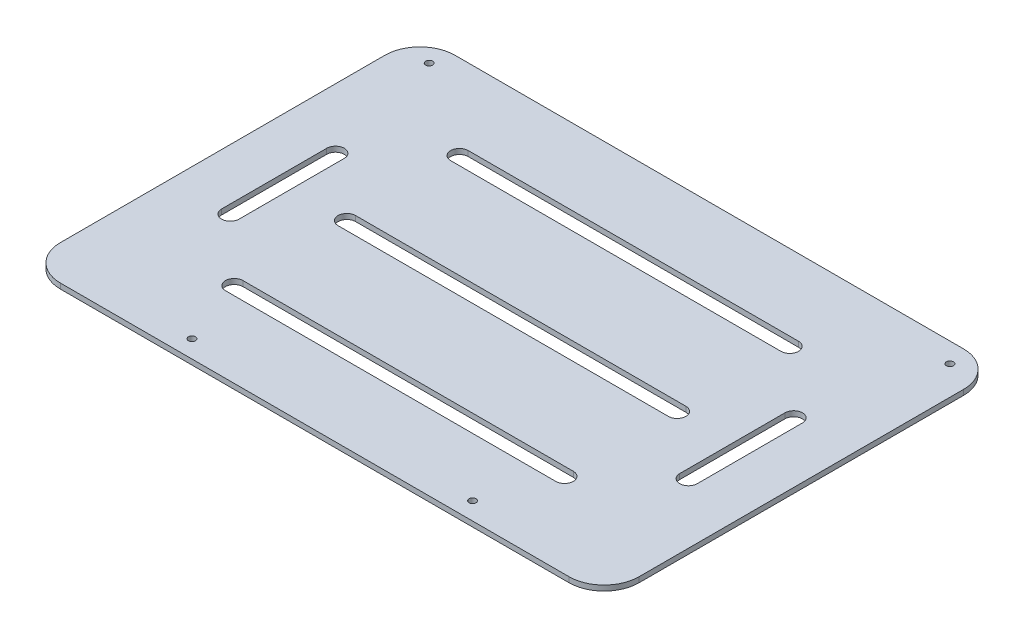
SolidWorks part; units mm, degrees
ref_plane "前视基准面" through (0, 0, 0) normal (0, 0, 1) x (1, 0, 0)
ref_plane "上视基准面" through (0, 0, 0) normal (0, 1, 0) x (1, 0, 0)
ref_plane "右视基准面" through (0, 0, 0) normal (1, 0, 0) x (0, 0, -1)
sketch "草图1" plane through (0, 0, 0) normal (0, 1, 0) x (1, 0, 0)
  line L1 (-145.5882, 128.3824) -> (184.4118, 128.3824)
  line L2 (-145.5882, 128.3824) -> (-145.5882, -96.6176)
  line L3 (-145.5882, -96.6176) -> (184.4118, -96.6176)
  line L4 (184.4118, 128.3824) -> (184.4118, -96.6176)
  dimension "D1" = 330
  dimension "D2" = 225
extrude "凸台-拉伸1" add sketch "草图1" along normal blind 3
sketch "草图2" plane through (0, 3, 0) normal (0, 1, 0) x (1, 0, 0)
  line L0 (-145.5882, 128.3824) -> (184.4118, -96.6176) construction
  line L1 (184.4118, 128.3824) -> (-145.5882, -96.6176) construction
sketch "草图3" plane through (0, 3, 0) normal (0, 1, 0) x (1, 0, 0)
  line L0 (-145.5882, 128.3824) -> (184.4118, -96.6176) construction
  line L1 (19.4118, 128.3824) -> (19.4118, -96.6176) construction
  line L2 (184.4118, 128.3824) -> (-145.5882, 128.3824) construction
  line L3 (-145.5882, -96.6176) -> (184.4118, -96.6176) construction
  line L5 (-145.5882, 15.8824) -> (184.4118, 15.8824) construction
  line L6 (-145.5882, 128.3824) -> (-145.5882, -96.6176) construction
  line L7 (184.4118, -96.6176) -> (184.4118, 128.3824) construction
  line L8 (19.4118, -86.6176) -> (50019.4118, -86.6176) construction
  circle A0 centre (-129.0637, 117.1156) radius 2
  circle A1 centre (167.8872, 117.1156) radius 2
  circle A2 centre (-60.5882, -86.6176) radius 2
  circle A3 centre (99.4118, -86.6176) radius 2
  dimension "D1" = 4
  dimension "D3" = 10
  dimension "D4" = 4
  dimension "D2" = 20
  dimension "D5" = 80
extrude "切除-拉伸1" cut sketch "草图3" against normal through all
sketch "草图4" plane through (0, 3, 0) normal (0, 1, 0) x (1, 0, 0)
  line L0 (-111.2352, 128.3824) -> (-111.2352, -96.6176) construction
  line L1 (184.4118, 128.3824) -> (-145.5882, 128.3824) construction
  line L2 (-145.5882, -96.6176) -> (184.4118, -96.6176) construction
  line L3 (19.4118, 128.3824) -> (19.4118, -96.6176) construction
  line L4 (150.0588, 128.3824) -> (150.0588, -96.6176) construction
  line L5 (-111.2352, -14.1176) -> (-111.2352, 45.8824) construction
  line L6 (-116.2352, -14.1176) -> (-116.2352, 45.8824)
  line L7 (-106.2352, -14.1176) -> (-106.2352, 45.8824)
  line L8 (150.0588, -14.1176) -> (150.0588, 45.8824) construction
  line L9 (155.0588, -14.1176) -> (155.0588, 45.8824)
  line L10 (145.0588, -14.1176) -> (145.0588, 45.8824)
  arc A0 (-116.2352, -14.1176) -> (-106.2352, -14.1176) centre (-111.2352, -14.1176) ccw
  arc A1 (-106.2352, 45.8824) -> (-116.2352, 45.8824) centre (-111.2352, 45.8824) ccw
  arc A2 (155.0588, -14.1176) -> (145.0588, -14.1176) centre (150.0588, -14.1176) cw
  arc A3 (145.0588, 45.8824) -> (155.0588, 45.8824) centre (150.0588, 45.8824) cw
  point P12 (-111.2352, 15.8824)
  point P19 (150.0588, 15.8824)
  dimension "D1" = 5
  dimension "D2" = 60
extrude "切除-拉伸2" cut sketch "草图4" against normal through all
sketch "草图5" plane through (0, 3, 0) normal (0, 1, 0) x (1, 0, 0)
  line L0 (-74.7746, 80.1003) -> (113.5981, 80.1003) construction
  line L1 (-145.5882, 128.3824) -> (184.4118, -96.6176) construction
  line L2 (184.4118, 128.3824) -> (-145.5882, -96.6176) construction
  line L3 (-74.7746, 85.1003) -> (113.5981, 85.1003)
  line L4 (-74.7746, 75.1003) -> (113.5981, 75.1003)
  line L5 (-145.5882, 15.8824) -> (184.4118, 15.8824) construction
  line L6 (-145.5882, 128.3824) -> (-145.5882, -96.6176) construction
  line L7 (184.4118, -96.6176) -> (184.4118, 128.3824) construction
  line L8 (-74.7746, -48.3356) -> (113.5981, -48.3356) construction
  line L9 (-74.7746, -53.3356) -> (113.5981, -53.3356)
  line L10 (-74.7746, -43.3356) -> (113.5981, -43.3356)
  arc A0 (-74.7746, 85.1003) -> (-74.7746, 75.1003) centre (-74.7746, 80.1003) ccw
  arc A1 (113.5981, 75.1003) -> (113.5981, 85.1003) centre (113.5981, 80.1003) ccw
  arc A2 (-74.7746, -53.3356) -> (-74.7746, -43.3356) centre (-74.7746, -48.3356) cw
  arc A3 (113.5981, -43.3356) -> (113.5981, -53.3356) centre (113.5981, -48.3356) cw
  point P6 (19.4118, 80.1003)
  point P11 (118.5981, 80.1003)
  point P21 (19.4118, -48.3356)
  dimension "D1" = 5
extrude "切除-拉伸3" cut sketch "草图5" against normal through all
sketch "草图6" plane through (0, 3, 0) normal (0, 1, 0) x (1, 0, 0)
  line L0 (-74.7732, 15.8824) -> (113.5968, 15.8824) construction
  line L1 (-145.5882, 128.3824) -> (184.4118, -96.6176) construction
  line L2 (-74.7732, 20.8824) -> (113.5968, 20.8824)
  line L3 (-74.7732, 10.8824) -> (113.5968, 10.8824)
  arc A0 (-74.7732, 20.8824) -> (-74.7732, 10.8824) centre (-74.7732, 15.8824) ccw
  arc A1 (113.5968, 10.8824) -> (113.5968, 20.8824) centre (113.5968, 15.8824) ccw
  point P4 (19.4118, 15.8824)
  dimension "D2" = 5
  dimension "D1" = 188.37
extrude "切除-拉伸4" cut sketch "草图6" against normal through all
fillet "圆角1" radius 20 4 edges at (184.4118, 1.5, 96.6176) (184.4118, 1.5, -128.3824) (-145.5882, 1.5, -128.3824) (-145.5882, 1.5, 96.6176)
